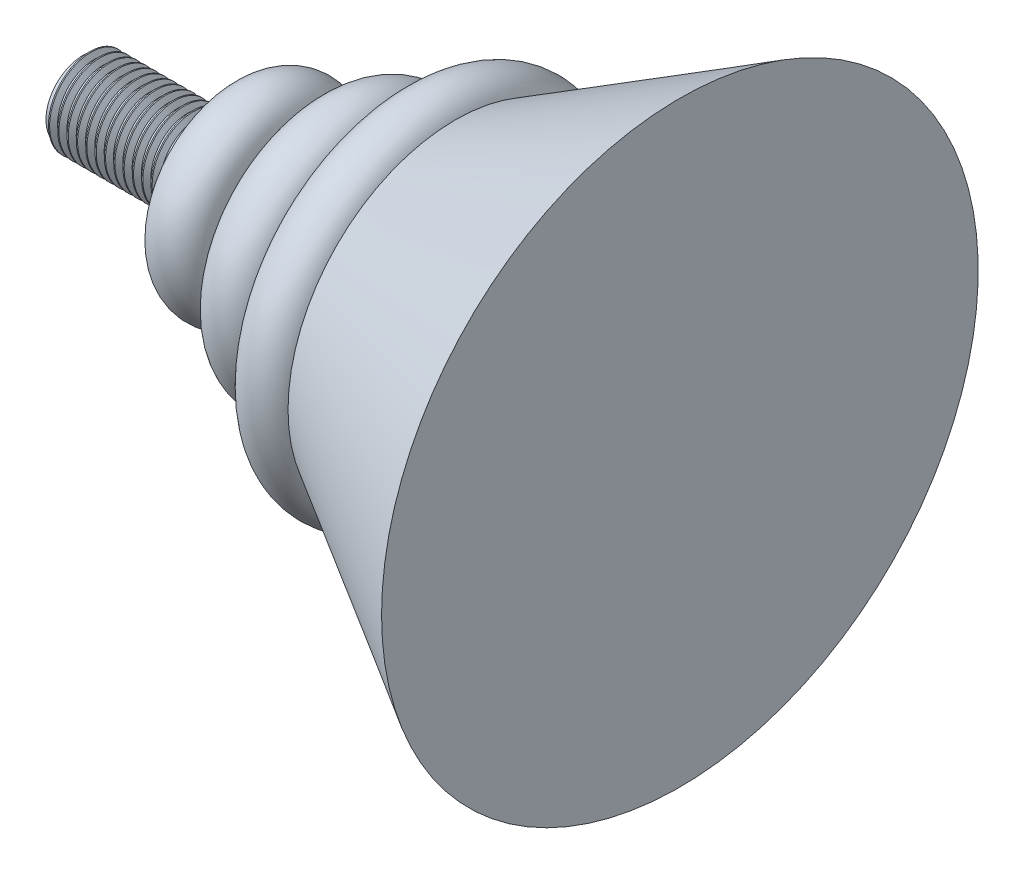
SolidWorks part; units mm, degrees
material "BUTYL"
ref_plane "Front Plane" through (0, 0, 0) normal (0, 0, 1) x (1, 0, 0)
ref_plane "Top Plane" through (0, 0, 0) normal (0, 1, 0) x (1, 0, 0)
ref_plane "Right Plane" through (0, 0, 0) normal (1, 0, 0) x (0, 0, -1)
sketch "Sketch1" plane through (0, 0, 0) normal (0, 0, 1) x (1, 0, 0)
  line L0 (-68.5646, 0) -> (11.4354, 0) construction
  line L1 (-68.5646, 0) -> (-68.5646, 5)
  line L2 (-68.5646, 5) -> (-48.5646, 5)
  line L4 (11.4354, 40) -> (11.4354, 0)
  line L5 (-68.5646, 0) -> (11.4354, 0)
  line L6 (-41.1139, 9.3462) -> (-36.795, 11.8656)
  line L7 (-29.8848, 15.8965) -> (-25.5659, 18.4159)
  line L8 (-18.6557, 22.4469) -> (11.4354, 40)
  line L11 (-48.5646, 5) -> (-48.5646, 11.5503)
  arc A0 (-48.5646, 11.5503) -> (-41.1139, 9.3462) centre (-45.1095, 9.5348) cw
  arc A1 (-36.795, 11.8656) -> (-29.8848, 15.8965) centre (-33.3399, 13.8811) cw
  arc A2 (-25.5659, 18.4159) -> (-18.6557, 22.4469) centre (-22.1108, 20.4314) cw
  dimension "D5" = 4
  dimension "D1" = 20
  dimension "D2" = 5
  dimension "D3" = 40
  dimension "D4" = 80
  dimension "D7" = 5
  dimension "D8" = 5
revolve "Revolve1" add sketch "Sketch1" angle 360 about L0
thread "Thread2" pitch 1.25 method extrude profile "Thread Profile3" start angle 0, offset 0, length 40, pitch 1.25, diameter 10
ref_plane "Plane3" through (-68.5646, 0, -5) normal (0, -1, 0) x (0, 0, -1)
sketch "Thread Profile3" plane through (-68.5646, 0, -5) normal (0, -1, 0) x (0, 0, -1)
  line L0 (0, 0) -> (0, 1.25) construction
  line L1 (0, 0) -> (0.6766, 0.3906)
  line L2 (0.6766, 0.3906) -> (0.6766, 0.5469)
  line L3 (0.6766, 0.5469) -> (0, 0.9375)
  line L4 (0.6766, 0.4687) -> (0, 0.4687) construction
  line L11 (0, 0) -> (0, 0.9375)
  point P2 (0, 0)
  dimension "Pitch" = 1.25
  dimension "Profile_Angle" = 60
  dimension "Profile_Land" = 0.1562
  dimension "Profile_Height" = 0.6766
